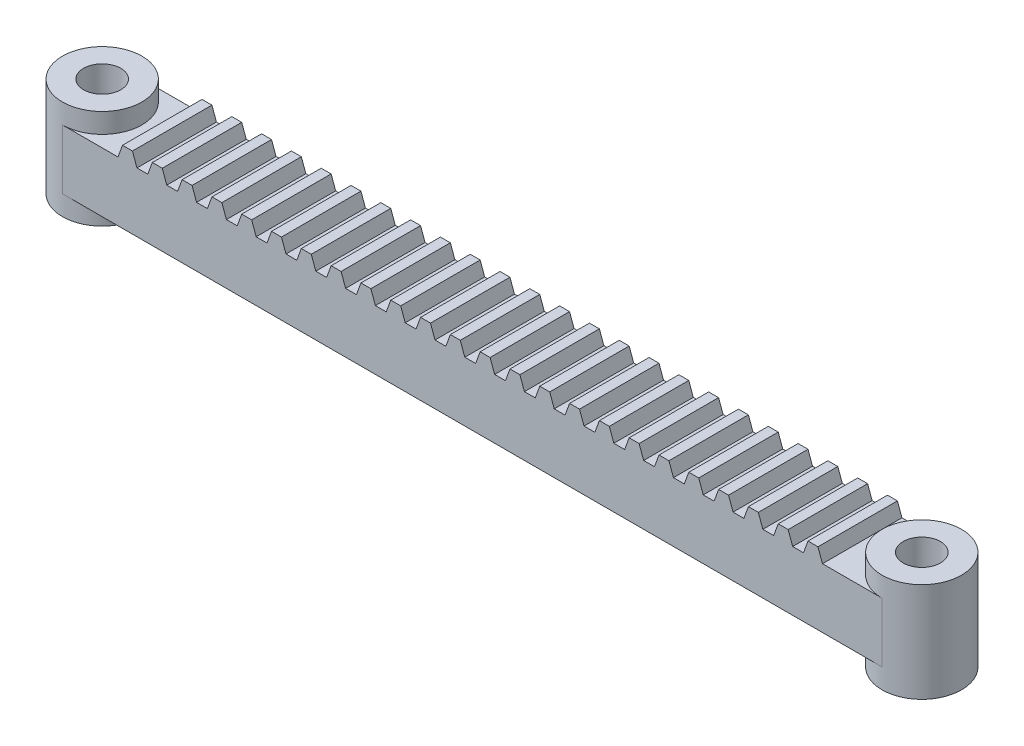
SolidWorks part; units mm, degrees
ref_plane "Front Plane" through (0, 0, 0) normal (0, 0, 1) x (1, 0, 0)
ref_plane "Top Plane" through (0, 0, 0) normal (0, 1, 0) x (1, 0, 0)
ref_plane "Right Plane" through (0, 0, 0) normal (1, 0, 0) x (0, 0, -1)
sketch "Sketch1" plane through (0, 0, 0) normal (0, 1, 0) x (1, 0, 0)
  line L0 (-601.7022, 0) -> (29483.4055, 0) construction
  line L1 (-82.5, -1000) -> (-82.5, 49000) construction
  circle A0 centre (0, 0) radius 8
  circle A1 centre (0, 0) radius 3.75
  circle A2 centre (-165, 0) radius 3.75
  circle A3 centre (-165, 0) radius 8
  point P7 (-82.5, 0)
  dimension "D1" = 16
  dimension "D2" = 7.5
  dimension "D3" = 82.5
extrude "Boss-Extrude1" add sketch "Sketch1" along normal blind 20
sketch "Sketch2" plane through (0, 0, 0) normal (0, 0, 1) x (1, 0, 0)
  line L0 (-1000, 0) -> (49000, 0) construction
  line L1 (0, 4) -> (-165, 4)
  line L2 (-152.9099, 18.5) -> (-151.9099, 18.5)
  line L3 (-150.9099, 18.5) -> (-151.9099, 18.5)
  line L4 (-165, 20) -> (-165, 0) construction
  line L5 (0, 20) -> (0, 0) construction
  line L6 (-165, 4) -> (-165, 11.6406)
  line L7 (0, 4) -> (0, 16)
  line L9 (-157, 0) -> (-157, 20) construction
  line L10 (-157, 16) -> (-153.8199, 16)
  line L11 (-153.8199, 16) -> (-152.9099, 18.5)
  line L12 (-150, 16) -> (-147.8199, 16)
  line L13 (-151.9099, -981.5) -> (-151.9099, 49018.5) construction
  line L14 (-150, 16) -> (-150.9099, 18.5)
  line L15 (-147.8199, 16) -> (-146.9099, 18.5)
  line L16 (-146.9099, 18.5) -> (-145.9099, 18.5)
  line L17 (-144.9099, 18.5) -> (-145.9099, 18.5)
  line L18 (-144, 16) -> (-144.9099, 18.5)
  line L19 (-141.8199, 16) -> (-140.9099, 18.5)
  line L20 (-140.9099, 18.5) -> (-139.9099, 18.5)
  line L21 (-138.9099, 18.5) -> (-139.9099, 18.5)
  line L22 (-138, 16) -> (-138.9099, 18.5)
  line L23 (-135.8199, 16) -> (-134.9099, 18.5)
  line L24 (-134.9099, 18.5) -> (-133.9099, 18.5)
  line L25 (-132.9099, 18.5) -> (-133.9099, 18.5)
  line L26 (-132, 16) -> (-132.9099, 18.5)
  line L27 (-129.8199, 16) -> (-128.9099, 18.5)
  line L28 (-128.9099, 18.5) -> (-127.9099, 18.5)
  line L29 (-126.9099, 18.5) -> (-127.9099, 18.5)
  line L30 (-126, 16) -> (-126.9099, 18.5)
  line L31 (-123.8199, 16) -> (-122.9099, 18.5)
  line L32 (-122.9099, 18.5) -> (-121.9099, 18.5)
  line L33 (-120.9099, 18.5) -> (-121.9099, 18.5)
  line L34 (-120, 16) -> (-120.9099, 18.5)
  line L35 (-117.8199, 16) -> (-116.9099, 18.5)
  line L36 (-116.9099, 18.5) -> (-115.9099, 18.5)
  line L37 (-114.9099, 18.5) -> (-115.9099, 18.5)
  line L38 (-114, 16) -> (-114.9099, 18.5)
  line L39 (-111.8199, 16) -> (-110.9099, 18.5)
  line L40 (-110.9099, 18.5) -> (-109.9099, 18.5)
  line L41 (-108.9099, 18.5) -> (-109.9099, 18.5)
  line L42 (-108, 16) -> (-108.9099, 18.5)
  line L43 (-105.8199, 16) -> (-104.9099, 18.5)
  line L44 (-104.9099, 18.5) -> (-103.9099, 18.5)
  line L45 (-102.9099, 18.5) -> (-103.9099, 18.5)
  line L46 (-102, 16) -> (-102.9099, 18.5)
  line L47 (-99.8199, 16) -> (-98.9099, 18.5)
  line L48 (-98.9099, 18.5) -> (-97.9099, 18.5)
  line L49 (-96.9099, 18.5) -> (-97.9099, 18.5)
  line L50 (-96, 16) -> (-96.9099, 18.5)
  line L51 (-93.8199, 16) -> (-92.9099, 18.5)
  line L52 (-92.9099, 18.5) -> (-91.9099, 18.5)
  line L53 (-90.9099, 18.5) -> (-91.9099, 18.5)
  line L54 (-90, 16) -> (-90.9099, 18.5)
  line L55 (-87.8199, 16) -> (-86.9099, 18.5)
  line L56 (-86.9099, 18.5) -> (-85.9099, 18.5)
  line L57 (-84.9099, 18.5) -> (-85.9099, 18.5)
  line L58 (-84, 16) -> (-84.9099, 18.5)
  line L59 (-81.8199, 16) -> (-80.9099, 18.5)
  line L60 (-80.9099, 18.5) -> (-79.9099, 18.5)
  line L61 (-78.9099, 18.5) -> (-79.9099, 18.5)
  line L62 (-78, 16) -> (-78.9099, 18.5)
  line L63 (-75.8199, 16) -> (-74.9099, 18.5)
  line L64 (-74.9099, 18.5) -> (-73.9099, 18.5)
  line L65 (-72.9099, 18.5) -> (-73.9099, 18.5)
  line L66 (-72, 16) -> (-72.9099, 18.5)
  line L67 (-69.8199, 16) -> (-68.9099, 18.5)
  line L68 (-68.9099, 18.5) -> (-67.9099, 18.5)
  line L69 (-66.9099, 18.5) -> (-67.9099, 18.5)
  line L70 (-66, 16) -> (-66.9099, 18.5)
  line L71 (-63.8199, 16) -> (-62.9099, 18.5)
  line L72 (-62.9099, 18.5) -> (-61.9099, 18.5)
  line L73 (-60.9099, 18.5) -> (-61.9099, 18.5)
  line L74 (-60, 16) -> (-60.9099, 18.5)
  line L75 (-57.8199, 16) -> (-56.9099, 18.5)
  line L76 (-56.9099, 18.5) -> (-55.9099, 18.5)
  line L77 (-54.9099, 18.5) -> (-55.9099, 18.5)
  line L78 (-54, 16) -> (-54.9099, 18.5)
  line L79 (-51.8199, 16) -> (-50.9099, 18.5)
  line L80 (-50.9099, 18.5) -> (-49.9099, 18.5)
  line L81 (-48.9099, 18.5) -> (-49.9099, 18.5)
  line L82 (-48, 16) -> (-48.9099, 18.5)
  line L83 (-45.8199, 16) -> (-44.9099, 18.5)
  line L84 (-44.9099, 18.5) -> (-43.9099, 18.5)
  line L85 (-42.9099, 18.5) -> (-43.9099, 18.5)
  line L86 (-42, 16) -> (-42.9099, 18.5)
  line L87 (-39.8199, 16) -> (-38.9099, 18.5)
  line L88 (-38.9099, 18.5) -> (-37.9099, 18.5)
  line L89 (-36.9099, 18.5) -> (-37.9099, 18.5)
  line L90 (-36, 16) -> (-36.9099, 18.5)
  line L91 (-33.8199, 16) -> (-32.9099, 18.5)
  line L92 (-32.9099, 18.5) -> (-31.9099, 18.5)
  line L93 (-30.9099, 18.5) -> (-31.9099, 18.5)
  line L94 (-30, 16) -> (-30.9099, 18.5)
  line L95 (-27.8199, 16) -> (-26.9099, 18.5)
  line L96 (-26.9099, 18.5) -> (-25.9099, 18.5)
  line L97 (-24.9099, 18.5) -> (-25.9099, 18.5)
  line L98 (-24, 16) -> (-24.9099, 18.5)
  line L99 (-21.8199, 16) -> (-20.9099, 18.5)
  line L100 (-20.9099, 18.5) -> (-19.9099, 18.5)
  line L101 (-18.9099, 18.5) -> (-19.9099, 18.5)
  line L102 (-18, 16) -> (-18.9099, 18.5)
  line L103 (-15.8199, 16) -> (-14.9099, 18.5)
  line L104 (-14.9099, 18.5) -> (-13.9099, 18.5)
  line L105 (-12.9099, 18.5) -> (-13.9099, 18.5)
  line L106 (-12, 16) -> (-12.9099, 18.5)
  line L107 (-144, 16) -> (-141.8199, 16)
  line L108 (-138, 16) -> (-135.8199, 16)
  line L109 (-132, 16) -> (-129.8199, 16)
  line L110 (-126, 16) -> (-123.8199, 16)
  line L111 (-120, 16) -> (-117.8199, 16)
  line L112 (-114, 16) -> (-111.8199, 16)
  line L113 (-108, 16) -> (-105.8199, 16)
  line L114 (-102, 16) -> (-99.8199, 16)
  line L115 (-96, 16) -> (-93.8199, 16)
  line L116 (-90, 16) -> (-87.8199, 16)
  line L117 (-84, 16) -> (-81.8199, 16)
  line L118 (-78, 16) -> (-75.8199, 16)
  line L119 (-72, 16) -> (-69.8199, 16)
  line L120 (-66, 16) -> (-63.8199, 16)
  line L121 (-60, 16) -> (-57.8199, 16)
  line L122 (-54, 16) -> (-51.8199, 16)
  line L123 (-48, 16) -> (-45.8199, 16)
  line L124 (-42, 16) -> (-39.8199, 16)
  line L125 (-36, 16) -> (-33.8199, 16)
  line L126 (-30, 16) -> (-27.8199, 16)
  line L127 (-24, 16) -> (-21.8199, 16)
  line L128 (-18, 16) -> (-15.8199, 16)
  line L129 (-12, 16) -> (0, 16)
  line L130 (-157, 16) -> (-165, 16)
  line L131 (-165, 16) -> (-165, 11.6406)
  point P11 (-157, 16)
  dimension "D1" = 4
  dimension "D2" = 12
  dimension "D3" = 2.5
  dimension "D4" = 40
  dimension "D5" = 1
  dimension "D6" = 12
  dimension "D7" = 6
  dimension "D9" = 23
  dimension "D10" = 12
  dimension "D8" = 24
extrude "Boss-Extrude2" add sketch "Sketch2" along normal mid plane 16
extrude "Boss-Extrude3" add sketch "Sketch1<4>" along normal blind 16
sketch "Sketch1<4>" plane through (0, 0, 0) normal (0, 1, 0) x (1, 0, 0) same geometry as "Sketch1"
ref_plane "Plane1" through (0, 0, 0) normal (0, -1, 0) x (-1, 0, 0)
sketch "Sketch3" plane through (0, 0, 0) normal (0, -1, 0) x (-1, 0, 0)
  circle A0 centre (165, 0) radius 3.75
  dimension "D1" = 7.5
extrude "Cut-Extrude2" cut sketch "Sketch3" against normal blind 16
ref_plane "Plane2" through (0, 0, 0) normal (0, -1, 0) x (-1, 0, 0)
sketch "Sketch4" plane through (0, 0, 0) normal (0, -1, 0) x (-1, 0, 0)
  circle A0 centre (0, 0) radius 3.75
  dimension "D1" = 7.5
extrude "Cut-Extrude3" cut sketch "Sketch4" against normal blind 16
